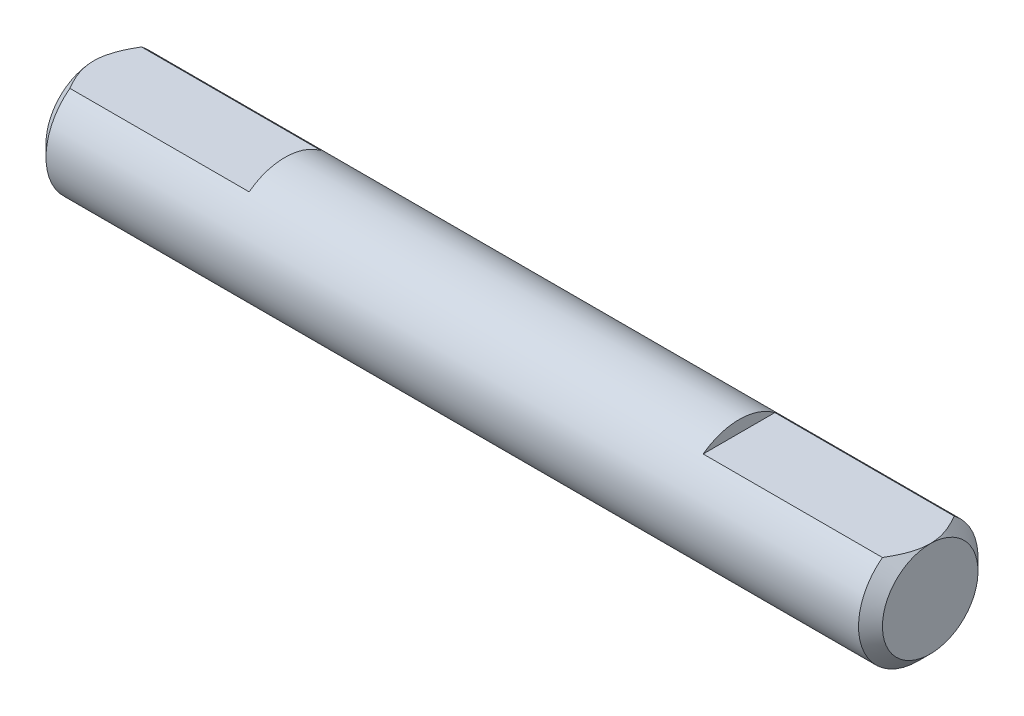
SolidWorks part; units mm, degrees
ref_plane "Front Plane" through (0, 0, 0) normal (0, 0, 1) x (1, 0, 0)
ref_plane "Top Plane" through (0, 0, 0) normal (0, 1, 0) x (1, 0, 0)
ref_plane "Right Plane" through (0, 0, 0) normal (1, 0, 0) x (0, 0, -1)
sketch "Sketch1" plane through (0, 0, 0) normal (1, 0, 0) x (0, 0, -1)
  circle A0 centre (0, 0) radius 2.5
  dimension "D1" = 5
extrude "Boss-Extrude1" add sketch "Sketch1" along normal mid plane 35
ref_plane "Plane1" through (9.5, 0, 0) normal (1, 0, 0) x (0, 0, -1)
sketch "Sketch2" plane through (9.5, 0, 0) normal (1, 0, 0) x (0, 0, -1)
  line L0 (-3.7024, 2) -> (4.0001, 2)
  line L1 (4.0001, 2) -> (4.0001, 3.9592)
  line L2 (4.0001, 3.9592) -> (-3.7024, 3.9592)
  line L3 (-3.7024, 3.9592) -> (-3.7024, 2)
  dimension "D1" = 2
extrude "Cut-Extrude1" cut sketch "Sketch2" along normal through all
mirror "Mirror1" about plane through (0, 0, 0) normal (1, 0, 0) of "Cut-Extrude1"
chamfer "Chamfer4" distance 0.5 angle 45 1 edges at (17.5, -2.5, 0)
chamfer "Chamfer5" distance 0.5 angle 45 1 edges at (-17.5, -2.5, 0)
